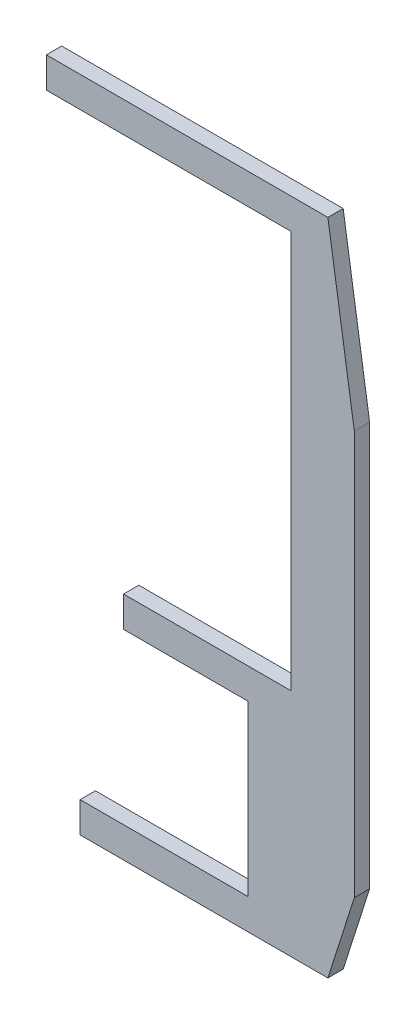
SolidWorks part; units mm, degrees
ref_plane "Front Plane" through (0, 0, 0) normal (0, 0, 1) x (1, 0, 0)
ref_plane "Top Plane" through (0, 0, 0) normal (0, 1, 0) x (1, 0, 0)
ref_plane "Right Plane" through (0, 0, 0) normal (1, 0, 0) x (0, 0, -1)
sketch "Sketch1" plane through (0, 0, 0) normal (0, 0, 1) x (1, 0, 0)
  line L0 (0, 0) -> (50.8, 0)
  line L1 (50.8, 0) -> (50.8, -82.55)
  line L2 (50.8, -82.55) -> (16.0069, -82.55)
  line L3 (16.0069, -82.55) -> (16.0069, -88.9)
  line L10 (63.9083, -29.3239) -> (58.42, 6.35)
  line L11 (58.42, 6.35) -> (0, 6.35)
  line L12 (0, 6.35) -> (0, 0)
  line L15 (63.9083, -113.1801) -> (63.9083, -29.3239)
  line L17 (16.0069, -88.9) -> (41.796, -88.9)
  line L18 (41.796, -88.9) -> (41.796, -124.0048)
  line L19 (41.796, -124.0048) -> (7.003, -124.0048)
  line L20 (7.003, -124.0048) -> (7.003, -130.3548)
  line L21 (7.003, -130.3548) -> (58.42, -130.3548)
  line L22 (58.42, -130.3548) -> (63.9083, -113.1801)
  point P7 (53.6552, -105.6034)
  dimension "D1" = 6.35
  dimension "D2" = 6.35
  dimension "D3" = 6.35
  dimension "D4" = 82.55
  dimension "D5" = 50.8
  dimension "D6" = 58.42
extrude "Boss-Extrude1" add sketch "Sketch1" along normal blind 3.175 contours L11 L12 L0 L1 L2 L3 L17 L18 L19 L20 L21 L22 L15 L10
